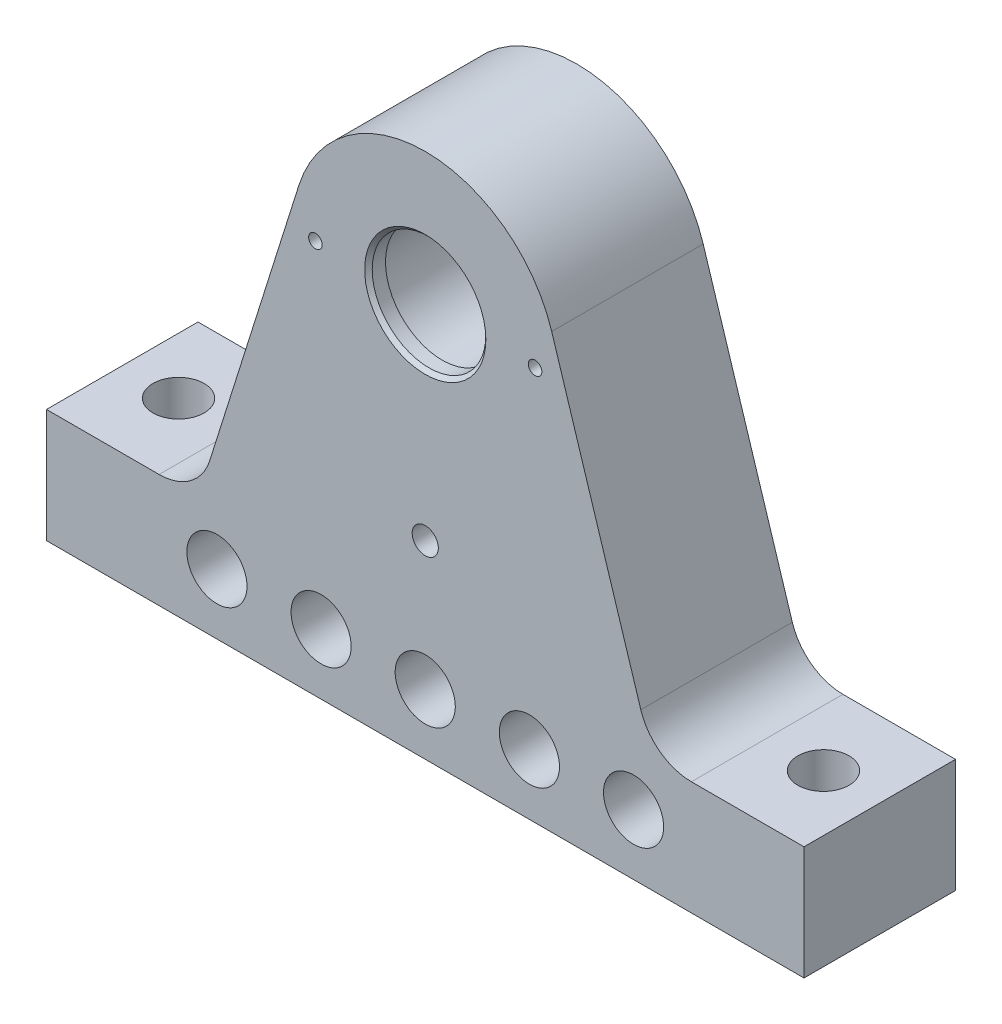
SolidWorks part; units mm, degrees
material "AISI 316 Annealed Stainless Steel Bar (SS)"
ref_plane "Front" through (0, 0, 0) normal (0, 0, 1) x (1, 0, 0)
ref_plane "Top" through (0, 0, 0) normal (0, 1, 0) x (1, 0, 0)
ref_plane "Right" through (0, 0, 0) normal (1, 0, 0) x (0, 0, -1)
sketch "Sketch1" plane through (0, 0, 0) normal (0, 0, 1) x (1, 0, 0)
  line L0 (-50, 0) -> (50, 0)
  line L1 (50, 0) -> (50, 15)
  line L3 (-50, 15) -> (-50, 0)
  line L4 (0, 0) -> (0, 52) construction
  line L5 (0, 52) -> (16.6918, 57.2568) construction
  line L6 (0, 52) -> (-16.6918, 57.2568) construction
  line L7 (50, 15) -> (30, 15)
  line L8 (-50, 15) -> (-30, 15)
  line L11 (-16.6918, 57.2568) -> (-30, 15)
  line L12 (16.6918, 57.2568) -> (30, 15)
  arc A0 (16.6918, 57.2568) -> (-16.6918, 57.2568) centre (0, 52) ccw
  circle A3 centre (0, 52) radius 4.7625 construction
  dimension "D3" = 17.5
  dimension "D6" = 9.525
  dimension "D1" = 100
  dimension "D2" = 52
  dimension "D4" = 15
  dimension "D5" = 20
extrude "Boss-Extrude1" add sketch "Sketch1" along normal blind 20
fillet "Fillet1" radius 7 2 edges at (30, 15, 10) (-30, 15, 10)
hole_wizard "CBORE for #8 Socket Head Cap Screw1" positions "Sketch2" profile "Sketch3" counterbore size "#8" standard "ANSI Inch" end condition through all
sketch "Sketch2" plane through (0, 0, 20) normal (0, 0, 1) x (1, 0, 0)
  line L0 (0, 0) -> (0, 8)
  line L1 (-50, 0) -> (50, 0) construction
  line L3 (-27.5, 8) -> (0, 8)
  line L5 (0, 8) -> (27.5, 8)
  point P0 (0, 8)
  point P21 (-27.5, 8)
  point P22 (-13.75, 8)
  point P24 (13.75, 8)
  point P28 (27.5, 8)
  dimension "D1" = 8
  dimension "D2" = 27.5
sketch "Sketch3" plane through (0, 8, 20) normal (1, 0, 0) x (0, -1, 0)
  line L0 (0, 0) -> (0, 20)
  line L1 (0, 20) -> (2.2479, 20)
  line L3 (2.2479, 20) -> (2.2479, 10)
  line L4 (2.2479, 10) -> (3.9687, 10)
  line L5 (3.9687, 10) -> (3.9687, 0)
  line L7 (3.9687, 0) -> (0, 0)
  line L11 (0, -6.35) -> (0, 107.95) construction
  dimension "Thru Hole Dia." = 4.4958
  dimension "Thru Hole Depth" = 20
  dimension "C'Bore Dia." = 7.9375
  dimension "C'Bore Depth" = 10
sketch "Sketch4" plane through (0, 0, 0) normal (1, 0, 0) x (0, 0, -1)
  line L0 (0, 52) -> (-20, 52)
  line L1 (-20, 52) -> (-20, 44.5)
  line L2 (-20, 44.5) -> (-17.75, 44.5)
  line L3 (-17.75, 44.5) -> (-17.75, 44)
  line L4 (-17.75, 44) -> (-7, 44)
  line L5 (-7, 44) -> (-7, 41)
  line L6 (-7, 41) -> (0, 41)
  line L7 (0, 0) -> (0, 52) construction
  line L8 (0, 41) -> (0, 52)
  point P3 (-10, 52)
  dimension "D1" = 11
  dimension "D2" = 8
  dimension "D3" = 7.5
  dimension "D4" = 2.25
  dimension "D5" = 7
revolve "Cut-Revolve1" cut sketch "Sketch4" angle 360 about L0
hole_wizard "#2-56 Tapped Hole1" positions "Sketch5" profile "Sketch6" tap size "#2-56" standard "ANSI Inch"
sketch "Sketch5" plane through (0, 0, 20) normal (0, 0, 1) x (1, 0, 0)
  line L0 (14.5, 52) -> (-14.5, 52) construction
  line L3 (0, 0) -> (0, 52) construction
  line L4 (-50, 0) -> (50, 0) construction
  circle A1 centre (0, 52) radius 7.5 construction
  point P0 (14.5, 52)
  point P2 (-14.5, 52)
  dimension "D1" = 29
sketch "Sketch6" plane through (14.5, 52, 20) normal (1, 0, 0) x (0, -1, 0)
  line L0 (0, 0) -> (0, 6.2642)
  line L1 (0, 6.2642) -> (0.889, 5.73)
  line L2 (0.889, 5.73) -> (0.889, 0)
  line L5 (0.889, 0) -> (0, 0)
  line L10 (0, 6.2642) -> (-0.889, 5.73) construction
  line L11 (0, -6.35) -> (0, 107.95) construction
  dimension "Tap Drill Dia." = 1.778
  dimension "Tap Drill Depth" = 5.73
  dimension "Drill Angle" = 118
cosmetic thread "Hole Thread1" parameters "D1"=4.37, "D2"=2.1844
cosmetic thread "Hole Thread2" parameters "D1"=4.37, "D2"=2.1844
chamfer "Chamfer1" distance 0.5 angle 45 2 edges at (-7.5, 52, 20) (-11, 52, 0)
hole_wizard "1/8 (0.1250) Dowel Hole1" positions "Sketch9" profile "Sketch10" hole size "1/8" standard "ANSI Inch"
sketch "Sketch9" plane through (0, 0, 0) normal (0, 0, -1) x (-1, 0, 0)
  line L0 (27.5, 8) -> (13.75, 8) construction
  point P0 (20.625, 8)
sketch "Sketch10" plane through (-20.625, 8, 0) normal (1, 0, 0) x (0, 1, 0)
  line L0 (0, 0) -> (0, 6.9539)
  line L1 (0, 6.9539) -> (1.5875, 6)
  line L2 (1.5875, 6) -> (1.5875, 0)
  line L5 (1.5875, 0) -> (0, 0)
  line L10 (0, 6.9539) -> (-1.5875, 6) construction
  line L11 (0, -6.35) -> (0, 107.95) construction
  dimension "Hole Dia." = 3.175
  dimension "Hole Depth" = 6
  dimension "Drill Angle" = 118
hole_wizard "1/8 (0.1250) Dowel Slot1" positions "Sketch11" profile "Sketch12" size "1/8" standard "ANSI Inch" slot yes
sketch "Sketch11" plane through (0, 0, 0) normal (0, 0, -1) x (-1, 0, 0)
  line L0 (-18.625, 8) -> (-22.625, 8) construction
  line L1 (-13.75, 8) -> (-27.5, 8) construction
  point P0 (-20.625, 8)
  dimension "D1" = 4
sketch "Sketch12" plane through (20.625, 8, 0) normal (1, 0, 0) x (0, 1, 0)
  line L0 (0, 0) -> (0, 6.9539)
  line L1 (0, 6.9539) -> (1.5875, 6)
  line L2 (1.5875, 6) -> (1.5875, 0)
  line L5 (1.5875, 0) -> (0, 0)
  line L10 (0, 6.9539) -> (-1.5875, 6) construction
  line L11 (0, -6.35) -> (0, 107.95) construction
  dimension "Hole Dia." = 3.175
  dimension "Hole Depth" = 6
  dimension "Drill Angle" = 118
sketch "Sketch13" plane through (0, 0, 0) normal (0, 0, -1) x (-1, 0, 0)
  circle A0 centre (0, 52) radius 10
  dimension "D1" = 20
extrude "Cut-Extrude1" [suppressed] cut sketch "Sketch13" along normal blind 1.1 from offset 2 offset against normal yes
hole_wizard "1/4 Clearance Hole1" positions "Sketch16" profile "Sketch17" hole size "1/4" standard "ANSI Inch" end condition through all
sketch "Sketch16" plane through (0, 15, 0) normal (0, 1, 0) x (1, 0, 0)
  line L0 (50, -10) -> (35.1344, -10) construction
  line L1 (50, -20) -> (50, 0) construction
  line L4 (-35.1344, -10) -> (-50, -10) construction
  line L6 (-50, -20) -> (-50, 0) construction
  line L7 (-35.1344, -20) -> (-35.1344, 0) construction
  line L8 (35.1344, 0) -> (35.1344, -20) construction
  point P0 (42.5672, -10)
  point P2 (-42.5672, -10)
sketch "Sketch17" plane through (42.5672, 15, 10) normal (1, 0, 0) x (0, 0, 1)
  line L0 (0, 0) -> (0, 15)
  line L1 (0, 15) -> (3.3782, 15)
  line L2 (3.3782, 15) -> (3.3782, 0)
  line L5 (3.3782, 0) -> (0, 0)
  line L11 (0, -6.35) -> (0, 107.95) construction
  dimension "Thru Hole Dia." = 6.7564
  dimension "Thru Hole Depth" = 15
hole_wizard "#8-32 Tapped Hole1" positions "Sketch18" profile "Sketch19" tap size "#8-32" standard "ANSI Inch"
sketch "Sketch18" plane through (0, 0, 20) normal (0, 0, 1) x (1, 0, 0)
  line L0 (0, 0) -> (0, 25) construction
  line L1 (-50, 0) -> (50, 0) construction
  point P0 (0, 25)
  dimension "D1" = 25
sketch "Sketch19" plane through (0, 25, 20) normal (1, 0, 0) x (0, -1, 0)
  line L0 (0, 0) -> (0, 11.7478)
  line L1 (0, 11.7478) -> (1.7272, 10.71)
  line L2 (1.7272, 10.71) -> (1.7272, 0)
  line L5 (1.7272, 0) -> (0, 0)
  line L10 (0, 11.7478) -> (-1.7272, 10.71) construction
  line L11 (0, -6.35) -> (0, 107.95) construction
  dimension "Tap Drill Dia." = 3.4544
  dimension "Tap Drill Depth" = 10.71
  dimension "Drill Angle" = 118
cosmetic thread "Hole Thread3" parameters "D1"=8.33, "D2"=4.1656
